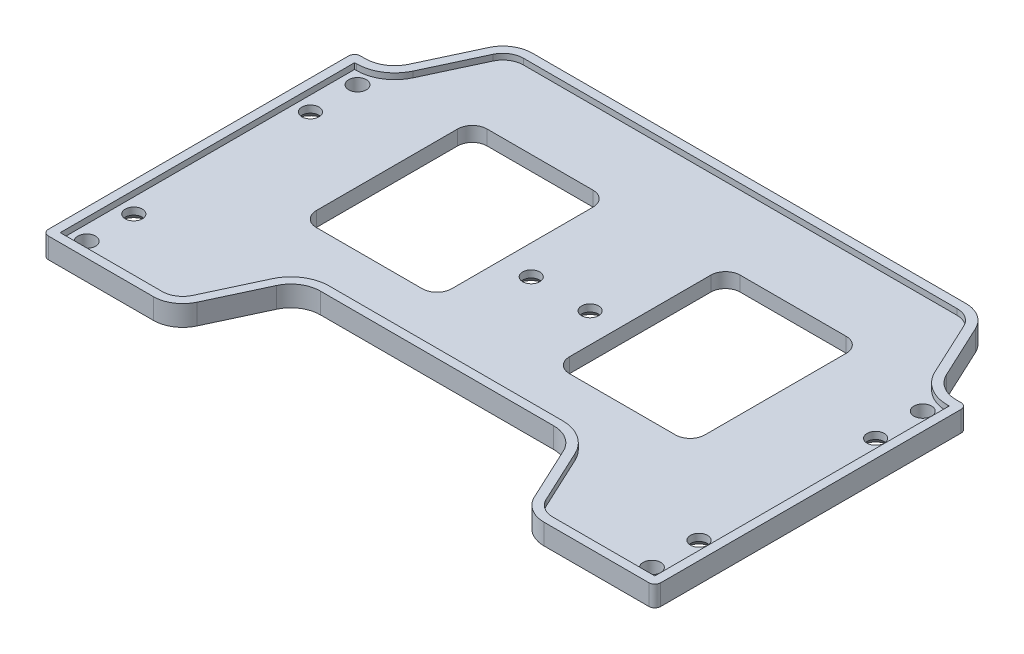
SolidWorks part; units mm, degrees
material "Delrin 2700 NC010, Low Viscosity Acetal Copolymer (SS)"
ref_plane "Front Plane" through (0, 0, 0) normal (0, 0, 1) x (1, 0, 0)
ref_plane "Top Plane" through (0, 0, 0) normal (0, 1, 0) x (1, 0, 0)
ref_plane "Right Plane" through (0, 0, 0) normal (1, 0, 0) x (0, 0, -1)
sketch "Sketch1" plane through (0, 0, 0) normal (0, 1, 0) x (1, 0, 0)
  line L0 (0, 0) -> (23, 0)
  line L1 (23, 0) -> (30, -15)
  line L2 (30, -15) -> (52, -15)
  line L3 (52, -15) -> (52, 38)
  line L4 (52, 38) -> (47, 38)
  line L5 (47, 38) -> (40, 53)
  line L6 (40, 53) -> (0, 53)
  line L7 (0, 53) -> (0, 0)
  dimension "D1" = 52
  dimension "D6" = 5
  dimension "D2" = 68
  dimension "D3" = 22
  dimension "D4" = 7
  dimension "D5" = 15
  dimension "D7" = 15
extrude "Boss-Extrude1" add sketch "Sketch1" along normal blind 3.5
fillet "Fillet1" radius 5 4 edges at (47, 1.75, -38) (40, 1.75, -53) (30, 1.75, 15) (23, 1.75, 0)
fillet "Fillet2" radius 1 2 edges at (52, 1.75, 15) (52, 1.75, -38)
hole_wizard "CSK for M2.5 Flat Head Machine Screw1" positions "Sketch5" profile "Sketch4" countersink size "M2.5" standard "ANSI Metric" end condition through all
sketch "Sketch5" plane through (0, 0, 0) normal (0, -1, 0) x (-1, 0, 0)
  line L0 (0, 0) -> (0, 53) construction
  line L3 (-33.1843, -15) -> (-51, -15) construction
  point P0 (-5, 21)
  point P2 (-48, -3.5)
  point P4 (-48, 26.5)
  dimension "D1" = 5
  dimension "D2" = 48
  dimension "D3" = 30
  dimension "D4" = 36
  dimension "D5" = 11.5
sketch "Sketch4" plane through (5, 0, -21) normal (1, 0, 0) x (0, 0, -1)
  line L0 (0, 0) -> (0, 3.5)
  line L1 (0, 3.5) -> (1.45, 3.5)
  line L2 (1.45, 3.5) -> (1.45, 1.3)
  line L3 (1.45, 1.3) -> (2.75, 0)
  line L5 (2.75, 0) -> (0, 0)
  line L6 (-1.45, 1.3) -> (-2.75, 0) construction
  line L11 (0, -6.35) -> (0, 107.95) construction
  dimension "Thru Hole Dia." = 2.9
  dimension "Thru Hole Depth" = 3.5
  dimension "Near C'Sink Dia." = 5.5
  dimension "Near C'Sink Angle" = 90
sketch "Sketch6" plane through (0, 0, 0) normal (0, -1, 0) x (1, 0, 0)
  line L2 (48, 3.5) -> (48, 11.5) construction
  line L3 (48, -26.5) -> (48, -34.5) construction
  circle A3 centre (48, 11.5) radius 1.5
  circle A4 centre (48, -34.5) radius 1.5
  point P9 (48, -26.5)
  dimension "D1" = 3
  dimension "D2" = 46
extrude "Cut-Extrude3" cut sketch "Sketch6" against normal through all
sketch "Sketch7" plane through (0, 3.5, 0) normal (0, 1, 0) x (1, 0, 0)
  line L0 (0, 0) -> (19.8157, 0) construction
  line L1 (10, 39) -> (33, 39)
  line L2 (10, 39) -> (10, 10)
  line L3 (10, 10) -> (33, 10)
  line L4 (33, 39) -> (33, 10)
  line L5 (0, 53) -> (0, 0) construction
  dimension "D1" = 29
  dimension "D2" = 23
  dimension "D3" = 10
  dimension "D4" = 10
extrude "Cut-Extrude4" cut sketch "Sketch7" against normal through all
fillet "Fillet3" radius 2.5 4 edges at (33, 1.75, -39) (33, 1.75, -10) (10, 1.75, -10) (10, 1.75, -39)
mirror "Mirror1" about plane through (0, 0, 0) normal (1, 0, 0) of "Fillet3", "Cut-Extrude3", "Fillet2", "Boss-Extrude1", "Fillet1", "CSK for M2.5 Flat Head Machine Screw1", "Cut-Extrude4"
sketch "Sketch2" plane through (0, 3.5, 0) normal (0, 1, 0) x (1, 0, 0)
  line L24 (-50.5, 36.5) -> (-50.5, -13.5)
  line L25 (-50.5, -13.5) -> (-33.1843, -13.5)
  line L26 (-30.0127, -11.4801) -> (-25.7059, -2.2512)
  line L27 (-19.8157, 1.5) -> (19.8157, 1.5)
  line L28 (25.7059, -2.2512) -> (30.0127, -11.4801)
  line L29 (33.1843, -13.5) -> (50.5, -13.5)
  line L30 (50.5, -13.5) -> (50.5, 36.5)
  line L31 (50.5, 36.5) -> (50.1843, 36.5)
  line L32 (44.2941, 40.2512) -> (39.9873, 49.4801)
  line L33 (36.8157, 51.5) -> (-36.8157, 51.5)
  line L34 (-39.9873, 49.4801) -> (-44.2941, 40.2512)
  line L35 (-50.1843, 36.5) -> (-50.5, 36.5)
  line L36 (-50.5, 36.5) -> (-50.5, -13.5)
  line L37 (-50.5, -13.5) -> (-33.1843, -13.5)
  line L38 (-30.0127, -11.4801) -> (-25.7059, -2.2512)
  line L39 (-19.8157, 1.5) -> (19.8157, 1.5)
  line L40 (25.7059, -2.2512) -> (30.0127, -11.4801)
  line L41 (33.1843, -13.5) -> (50.5, -13.5)
  line L42 (50.5, -13.5) -> (50.5, 36.5)
  line L43 (50.5, 36.5) -> (50.1843, 36.5)
  line L44 (44.2941, 40.2512) -> (39.9873, 49.4801)
  line L45 (36.8157, 51.5) -> (-36.8157, 51.5)
  line L46 (-39.9873, 49.4801) -> (-44.2941, 40.2512)
  line L47 (-50.1843, 36.5) -> (-50.5, 36.5)
  arc A24 (-33.1843, -13.5) -> (-30.0127, -11.4801) centre (-33.1843, -10) ccw
  arc A25 (-19.8157, 1.5) -> (-25.7059, -2.2512) centre (-19.8157, -5) ccw
  arc A26 (25.7059, -2.2512) -> (19.8157, 1.5) centre (19.8157, -5) ccw
  arc A27 (30.0127, -11.4801) -> (33.1843, -13.5) centre (33.1843, -10) ccw
  arc A28 (44.2941, 40.2512) -> (50.1843, 36.5) centre (50.1843, 43) ccw
  arc A29 (39.9873, 49.4801) -> (36.8157, 51.5) centre (36.8157, 48) ccw
  arc A30 (-36.8157, 51.5) -> (-39.9873, 49.4801) centre (-36.8157, 48) ccw
  arc A31 (-50.1843, 36.5) -> (-44.2941, 40.2512) centre (-50.1843, 43) ccw
  arc A32 (-33.1843, -13.5) -> (-30.0127, -11.4801) centre (-33.1843, -10) ccw
  arc A33 (-19.8157, 1.5) -> (-25.7059, -2.2512) centre (-19.8157, -5) ccw
  arc A34 (25.7059, -2.2512) -> (19.8157, 1.5) centre (19.8157, -5) ccw
  arc A35 (30.0127, -11.4801) -> (33.1843, -13.5) centre (33.1843, -10) ccw
  arc A36 (44.2941, 40.2512) -> (50.1843, 36.5) centre (50.1843, 43) ccw
  arc A37 (39.9873, 49.4801) -> (36.8157, 51.5) centre (36.8157, 48) ccw
  arc A38 (-36.8157, 51.5) -> (-39.9873, 49.4801) centre (-36.8157, 48) ccw
  arc A39 (-50.1843, 36.5) -> (-44.2941, 40.2512) centre (-50.1843, 43) ccw
  dimension "D1" = 1.5
extrude "Cut-Extrude2" cut sketch "Sketch2" against normal blind 1
